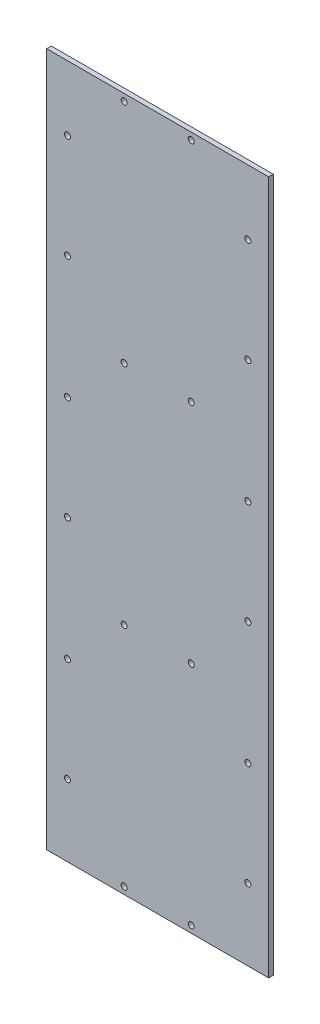
SolidWorks part; units mm, degrees
material "Alumina"
ref_plane "Front Plane" through (0, 0, 0) normal (0, 0, 1) x (1, 0, 0)
ref_plane "Top Plane" through (0, 0, 0) normal (0, 1, 0) x (1, 0, 0)
ref_plane "Right Plane" through (0, 0, 0) normal (1, 0, 0) x (0, 0, -1)
sketch "Sketch1" plane through (0, 0, 0) normal (0, 0, 1) x (1, 0, 0)
  line L1 (48, -150) -> (-48, -150)
  line L2 (48, -150) -> (48, 150)
  line L3 (48, 150) -> (-48, 150)
  line L4 (-48, -150) -> (-48, 150)
  line L5 (48, -150) -> (-48, 150) construction
  line L6 (48, 150) -> (-48, -150) construction
  point P0 (0, 0)
  dimension "D1" = 96
  dimension "D2" = 300
extrude "Boss-Extrude1" add sketch "Sketch1" along normal blind 2
sketch "Sketch2" plane through (0, 0, 2) normal (0, 0, 1) x (1, 0, 0)
  line L0 (-48, 150) -> (-48, -150) construction
  line L1 (48, 150) -> (-48, 150) construction
  line L2 (-48, -150) -> (48, -150) construction
  line L3 (48, -150) -> (48, 150) construction
  line L4 (0, -1.1) -> (0, 1.1) construction
  circle A0 centre (-39, 122) radius 1.3
  circle A1 centre (-39, 77) radius 1.3
  circle A2 centre (39, 122) radius 1.3
  circle A3 centre (39, 77) radius 1.3
  circle A4 centre (-39, 24) radius 1.3
  circle A5 centre (-39, -21) radius 1.3
  circle A6 centre (39, 24) radius 1.3
  circle A7 centre (39, -21) radius 1.3
  circle A8 centre (-39, -74) radius 1.3
  circle A9 centre (-39, -119) radius 1.3
  circle A10 centre (39, -74) radius 1.3
  circle A11 centre (39, -119) radius 1.3
  circle A13 centre (14.5, -147) radius 1.3
  circle A14 centre (-14.5, -147) radius 1.3
  circle A15 centre (-14.5, -49) radius 1.3
  circle A16 centre (14.5, -49) radius 1.3
  circle A17 centre (-14.5, 49) radius 1.3
  circle A18 centre (14.5, 49) radius 1.3
  circle A19 centre (-14.5, 147) radius 1.3
  circle A20 centre (14.5, 147) radius 1.3
  point P50 (0, 0)
  dimension "D1" = 2.6
  dimension "D3" = 28
  dimension "D4" = 2.6
  dimension "D6" = 9
  dimension "D10" = 2.6
  dimension "D11" = 33.5
  dimension "D13" = 3
  dimension "D15" = 9
  dimension "D2" = 9
  dimension "D5" = 45
  dimension "D9" = 31
  dimension "D14" = 9
  dimension "D16" = 3
  dimension "D7" = 2
  dimension "D8" = 3
  dimension "D12" = 4
extrude "Cut-Extrude1" cut sketch "Sketch2" against normal blind 10
